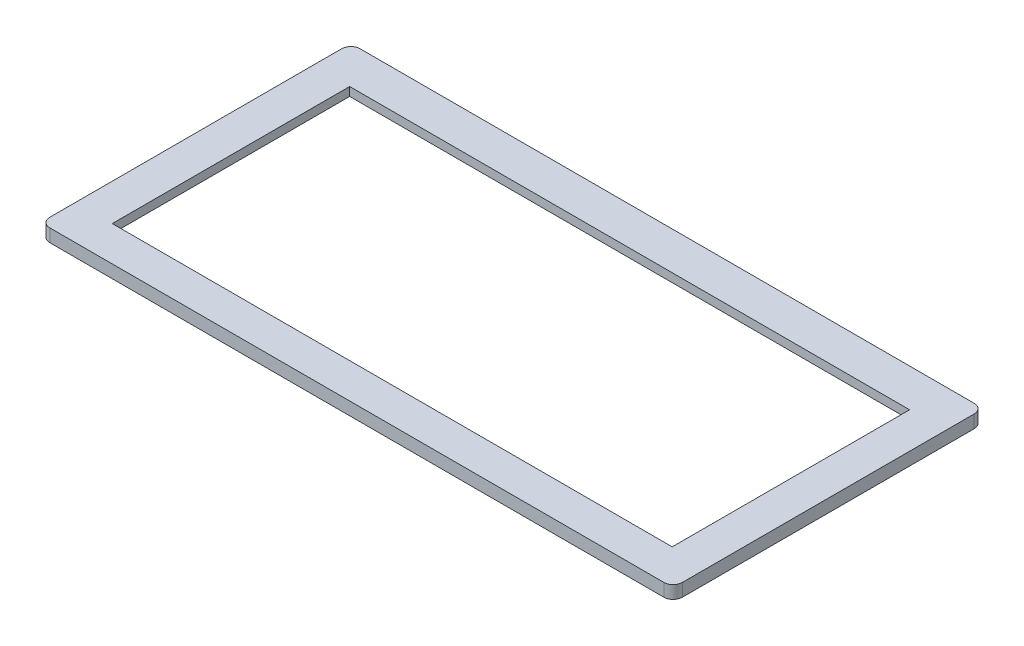
SolidWorks part; units mm, degrees
ref_plane "Front Plane" through (0, 0, 0) normal (0, 0, 1) x (1, 0, 0)
ref_plane "Top Plane" through (0, 0, 0) normal (0, 1, 0) x (1, 0, 0)
ref_plane "Right Plane" through (0, 0, 0) normal (1, 0, 0) x (0, 0, -1)
sketch "Sketch1" plane through (0, 0, 0) normal (0, 1, 0) x (1, 0, 0)
  line L0 (-142.8618, 0) -> (191.3602, 0) construction
  line L1 (0, 90.7825) -> (0, -132.7671) construction
  line L2 (-160.275, 78.7825) -> (160.275, 78.7825)
  line L3 (160.275, 78.7825) -> (160.275, -66.2175)
  line L4 (160.275, -66.2175) -> (-160.275, -66.2175)
  line L5 (-160.275, -66.2175) -> (-160.275, 78.7825)
  line L6 (-172.275, 90.7825) -> (172.275, 90.7825)
  line L7 (172.275, 90.7825) -> (172.275, -78.2175)
  line L8 (172.275, -78.2175) -> (-172.275, -78.2175)
  line L9 (-172.275, -78.2175) -> (-172.275, 90.7825)
  dimension "D1" = 320.55
  dimension "D2" = 145
  dimension "D3" = 12
  dimension "D4" = 12
  dimension "D5" = 12
  dimension "D6" = 12
extrude "Boss-Extrude1" add sketch "Sketch1" along normal blind 7
sketch "Sketch3" plane through (0, 0, 0) normal (0, -1, 0) x (1, 0, 0)
  line L0 (-22.72, -82.0825) -> (-47.57, -82.0825)
  line L1 (-22.72, -86.5825) -> (-22.72, -82.0825)
  line L2 (-78.72, -86.5825) -> (-22.72, -86.5825)
  line L3 (-78.72, -82.0825) -> (-78.72, -86.5825)
  line L4 (-53.87, -82.0825) -> (-78.72, -82.0825)
  line L5 (-53.87, -78.7825) -> (-53.87, -82.0825)
  line L6 (-47.57, -78.7825) -> (-53.87, -78.7825)
  line L7 (-47.57, -82.0825) -> (-47.57, -78.7825)
  line L16 (160.275, -78.7825) -> (-160.275, -78.7825) construction
  line L17 (-130.175, 66.2175) -> (-123.875, 66.2175)
  line L18 (146.225, -82.0825) -> (121.375, -82.0825)
  line L19 (146.225, -86.5825) -> (146.225, -82.0825)
  line L20 (90.225, -86.5825) -> (146.225, -86.5825)
  line L21 (90.225, -82.0825) -> (90.225, -86.5825)
  line L22 (115.075, -82.0825) -> (90.225, -82.0825)
  line L23 (115.075, -78.7825) -> (115.075, -82.0825)
  line L24 (121.375, -78.7825) -> (115.075, -78.7825)
  line L25 (121.375, -82.0825) -> (121.375, -78.7825)
  line L26 (71.33, -86.5825) -> (71.33, -82.0825)
  line L27 (15.33, -86.5825) -> (71.33, -86.5825)
  line L28 (15.33, -82.0825) -> (15.33, -86.5825)
  line L29 (40.18, -82.0825) -> (15.33, -82.0825)
  line L30 (40.18, -78.7825) -> (40.18, -82.0825)
  line L31 (46.48, -78.7825) -> (40.18, -78.7825)
  line L32 (46.48, -82.0825) -> (46.48, -78.7825)
  line L33 (71.33, -82.0825) -> (46.48, -82.0825)
  line L34 (-160.275, -78.7825) -> (-160.275, -50.3825) construction
  line L43 (-160.275, -44.0825) -> (-160.275, -50.3825)
  line L44 (-160.275, -44.0825) -> (-163.575, -44.0825)
  line L53 (163.575, 11.9175) -> (163.575, 32.2175)
  line L54 (-160.275, 66.2175) -> (160.275, 66.2175) construction
  line L55 (160.275, 66.2175) -> (160.275, -78.7825) construction
  line L56 (151.2867, -7.345) -> (183.3703, -7.345) construction
  line L57 (0, 81.7249) -> (0, 49.7201) construction
  line L58 (160.275, -40.5825) -> (163.575, -40.5825)
  line L59 (163.575, -40.5825) -> (163.575, -15.7325)
  line L60 (163.575, -15.7325) -> (168.075, -15.7325)
  line L61 (168.075, -15.7325) -> (168.075, -71.7325)
  line L62 (168.075, -71.7325) -> (163.575, -71.7325)
  line L63 (163.575, -71.7325) -> (163.575, -46.8825)
  line L64 (160.275, -46.8825) -> (163.575, -46.8825)
  line L65 (160.275, -40.5825) -> (160.275, -46.8825)
  line L66 (160.275, 32.2175) -> (163.575, 32.2175)
  line L68 (163.575, 58.8175) -> (168.075, 58.8175)
  line L69 (168.075, 58.8175) -> (168.075, 11.9175)
  line L70 (168.075, 11.9175) -> (163.575, 11.9175)
  line L72 (160.275, 38.5175) -> (163.575, 38.5175)
  line L73 (160.275, 32.2175) -> (160.275, 38.5175)
  line L74 (146.225, 74.0175) -> (146.225, 69.5175)
  line L75 (90.225, 74.0175) -> (146.225, 74.0175)
  line L76 (90.225, 69.5175) -> (90.225, 74.0175)
  line L77 (115.075, 69.5175) -> (90.225, 69.5175)
  line L78 (115.075, 66.2175) -> (115.075, 69.5175)
  line L79 (121.375, 66.2175) -> (115.075, 66.2175)
  line L80 (121.375, 69.5175) -> (121.375, 66.2175)
  line L81 (146.225, 69.5175) -> (121.375, 69.5175)
  line L82 (15.33, 74.0175) -> (71.33, 74.0175)
  line L83 (15.33, 69.5175) -> (15.33, 74.0175)
  line L84 (40.18, 69.5175) -> (15.33, 69.5175)
  line L85 (40.18, 66.2175) -> (40.18, 69.5175)
  line L86 (46.48, 66.2175) -> (40.18, 66.2175)
  line L87 (46.48, 69.5175) -> (46.48, 66.2175)
  line L88 (71.33, 69.5175) -> (46.48, 69.5175)
  line L89 (71.33, 74.0175) -> (71.33, 69.5175)
  line L106 (0, -99.7125) -> (0, -58.961) construction
  line L115 (163.575, 38.5175) -> (163.575, 58.8175)
  line L116 (-160.275, 66.2175) -> (160.275, 66.2175) construction
  line L117 (-160.275, -50.3825) -> (-163.575, -50.3825)
  line L118 (-163.575, -44.0825) -> (-163.575, -19.2325)
  line L119 (-163.575, -50.3825) -> (-163.575, -75.2325)
  line L120 (-163.575, -19.2325) -> (-168.075, -19.2325)
  line L121 (-168.075, -19.2325) -> (-168.075, -75.2325)
  line L122 (-168.075, -75.2325) -> (-163.575, -75.2325)
  line L123 (-160.275, -78.7825) -> (-160.275, 66.2175) construction
  line L124 (-160.275, 38.5175) -> (-160.275, 32.2175)
  line L125 (-160.275, 38.5175) -> (-163.575, 38.5175)
  line L126 (-160.275, 32.2175) -> (-163.575, 32.2175)
  line L127 (-163.575, 38.5175) -> (-163.575, 58.8175)
  line L128 (-163.575, 58.8175) -> (-168.075, 58.8175)
  line L129 (-168.075, 58.8175) -> (-168.075, 11.9175)
  line L130 (-168.075, 11.9175) -> (-163.575, 11.9175)
  line L131 (-163.575, 11.9175) -> (-163.575, 32.2175)
  line L132 (-160.275, 66.2175) -> (-160.275, 38.5175) construction
  line L133 (-123.875, 66.2175) -> (-123.875, 69.5175)
  line L134 (-123.875, 69.5175) -> (-99.025, 69.5175)
  line L135 (-99.025, 69.5175) -> (-99.025, 74.0175)
  line L136 (-99.025, 74.0175) -> (-155.025, 74.0175)
  line L137 (-155.025, 74.0175) -> (-155.025, 69.5175)
  line L138 (-155.025, 69.5175) -> (-130.175, 69.5175)
  line L139 (-130.175, 69.5175) -> (-130.175, 66.2175)
  line L140 (-160.275, 66.2175) -> (-130.175, 66.2175) construction
  line L141 (-55.375, 66.2175) -> (-49.075, 66.2175)
  line L142 (-49.075, 66.2175) -> (-49.075, 69.5175)
  line L143 (-49.075, 69.5175) -> (-24.225, 69.5175)
  line L144 (-24.225, 69.5175) -> (-24.225, 74.0175)
  line L145 (-24.225, 74.0175) -> (-80.225, 74.0175)
  line L146 (-80.225, 74.0175) -> (-80.225, 69.5175)
  line L147 (-80.225, 69.5175) -> (-55.375, 69.5175)
  line L148 (-55.375, 69.5175) -> (-55.375, 66.2175)
  line L149 (-123.875, 66.2175) -> (-55.375, 66.2175) construction
  line L150 (-47.57, -78.7825) -> (0, -78.7825) construction
  line L151 (160.275, -78.7825) -> (-160.275, -78.7825) construction
  line L152 (0, -78.7825) -> (40.18, -78.7825) construction
  dimension "D5" = 6.3
  dimension "D6" = 4.5
  dimension "D7" = 56
  dimension "D8" = 6.3
  dimension "D9" = 6.3
  dimension "D10" = 3.3
  dimension "D11" = 56
  dimension "D12" = 47.57
  dimension "D13" = 6.3
  dimension "D14" = 4.5
  dimension "D15" = 56
  dimension "D16" = 6.3
  dimension "D17" = 6.3
  dimension "D18" = 4.5
  dimension "D19" = 56
  dimension "D20" = 3.3
  dimension "D21" = 28.4
  dimension "D22" = 20.3
  dimension "D23" = 4.5
  dimension "D24" = 3.3
  dimension "D25" = 27.7
  dimension "D26" = 3.3
  dimension "D27" = 4.5
  dimension "D28" = 56
  dimension "D29" = 30.1
  dimension "D30" = 40.18
  dimension "D31" = 180
  dimension "56" = 56
  dimension "D32" = 6.3
  dimension "D33" = 38.9
  dimension "D34" = 6.3
  dimension "D35" = 27.7
  dimension "D36" = 31.9
  dimension "D37" = 56
  dimension "D38" = 38.9
  dimension "D39" = 6.3
  dimension "D40" = 3.3
  dimension "D41" = 4.5
  dimension "D42" = 40.18
  dimension "D43" = 6.3
  dimension "D44" = 3.3
  dimension "D45" = 46.9
  dimension "D46" = 6.3
  dimension "D47" = 3.3
  dimension "D48" = 4.5
  dimension "D49" = 3.3
  dimension "D50" = 4.5
  dimension "D51" = 3.3
  dimension "D52" = 4.5
  dimension "D53" = 56
  dimension "D54" = 4.5
  dimension "D55" = 3.3
  dimension "D56" = 4.5
  dimension "D57" = 3.3
  dimension "D58" = 56
  dimension "D59" = 68.5
  dimension "D60" = 180
fillet "Fillet1" radius 5 1 edges at (172.275, 3.5, 78.2175)
fillet "Fillet2" radius 5 1 edges at (-172.275, 3.5, -90.7825)
fillet "Fillet3" radius 5 1 edges at (-172.275, 3.5, 78.2175)
extrude "Cut-Extrude2" cut sketch "Sketch3" against normal blind 2.3
fillet "Fillet5" radius 5 1 edges at (172.275, 3.5, -90.7825)
sketch "Sketch4" plane through (0, 0, 0) normal (0, -1, 0) x (1, 0, 0)
  circle A8 centre (-165.5428, 71.4853) radius 1.325
  circle A9 centre (-89.625, 71.7675) radius 1.325
  circle A10 centre (80.7775, 71.7675) radius 1.325
  circle A11 centre (165.5328, 71.4853) radius 1.325
  circle A12 centre (165.5328, -84.0502) radius 1.325
  circle A13 centre (80.7775, -84.3325) radius 1.325
  circle A14 centre (-89.625, -84.0502) radius 1.325
  circle A15 centre (-165.5428, -84.0502) radius 1.325
  point P6 (-165.5428, 71.4853)
  point P7 (-89.625, 71.7675)
  point P9 (80.7775, 71.7675)
  point P11 (80.7775, -84.3325)
  point P12 (-89.625, -84.0502)
  point P13 (-165.5428, -84.0502)
  point P16 (165.5328, 71.4853)
  point P22 (165.5328, -84.0502)
extrude "Cut-Extrude3" cut sketch "Sketch4" against normal blind 5
fillet "Fillet6" radius 3 66 edges at (-78.72, 1.15, -86.5825) (-78.72, 1.15, -82.0825) (-22.72, 1.15, -86.5825) (-22.72, 1.15, -82.0825) (-53.87, 1.15, -82.0825) (-47.57, 1.15, -82.0825) (15.33, 1.15, -86.5825) (15.33, 1.15, -82.0825) (71.33, 1.15, -86.5825) (71.33, 1.15, -82.0825) (40.18, 1.15, -82.0825) (46.48, 1.15, -82.0825) (90.225, 1.15, -86.5825) (90.225, 1.15, -82.0825) (146.225, 1.15, -86.5825) (146.225, 1.15, -82.0825) (115.075, 1.15, -82.0825) (121.375, 1.15, -82.0825) (163.575, 1.15, -71.7325) (168.075, 1.15, -71.7325) (168.075, 1.15, -15.7325) (163.575, 1.15, -15.7325) (163.575, 1.15, -46.8825) (163.575, 1.15, -40.5825) (163.575, 1.15, 11.9175) (168.075, 1.15, 11.9175) (163.575, 1.15, 58.8175) (168.075, 1.15, 58.8175) (163.575, 1.15, 32.2175) (163.575, 1.15, 38.5175) (146.225, 1.15, 69.5175) (146.225, 1.15, 74.0175) (90.225, 1.15, 74.0175) (90.225, 1.15, 69.5175) (115.075, 1.15, 69.5175) (121.375, 1.15, 69.5175) (71.33, 1.15, 69.5175) (71.33, 1.15, 74.0175) (15.33, 1.15, 69.5175) (15.33, 1.15, 74.0175) (46.48, 1.15, 69.5175) (40.18, 1.15, 69.5175) (-24.225, 1.15, 69.5175) (-24.225, 1.15, 74.0175) (-80.225, 1.15, 74.0175) (-80.225, 1.15, 69.5175) (-49.075, 1.15, 69.5175) (-55.375, 1.15, 69.5175) (-155.025, 1.15, 69.5175) (-155.025, 1.15, 74.0175) (-99.025, 1.15, 69.5175) (-99.025, 1.15, 74.0175) (-123.875, 1.15, 69.5175) (-130.175, 1.15, 69.5175) (-163.575, 1.15, 11.9175) (-168.075, 1.15, 11.9175) (-168.075, 1.15, 58.8175) (-163.575, 1.15, 58.8175) (-163.575, 1.15, 38.5175) (-163.575, 1.15, 32.2175) (-163.575, 1.15, -19.2325) (-168.075, 1.15, -19.2325) (-168.075, 1.15, -75.2325) (-163.575, 1.15, -75.2325) (-163.575, 1.15, -50.3825) (-163.575, 1.15, -44.0825)
sketch "Sketch5" plane through (0, 7, 0) normal (0, 1, 0) x (1, 0, 0)
  line L0 (-160.275, 78.7825) -> (-160.275, -66.2175)
  line L1 (-160.275, -66.2175) -> (160.275, -66.2175)
  line L2 (160.275, -66.2175) -> (160.275, 78.7825)
  line L3 (160.275, 78.7825) -> (-160.275, 78.7825)
  line L4 (-152.275, 70.1325) -> (-152.275, -59.1715)
  line L5 (-152.275, -59.1715) -> (152.725, -59.1715)
  line L6 (152.725, -59.1715) -> (152.725, 70.1325)
  line L7 (152.725, 70.1325) -> (-152.275, 70.1325)
  line L22 (-124.288, -55.6715) -> (-110.288, -55.6715) construction
  dimension "D1" = 8
  dimension "D2" = 3.5
  dimension "D3" = 8.65
  dimension "D4" = 7.55
extrude "Boss-Extrude2" add sketch "Sketch5" against normal blind 4.7
